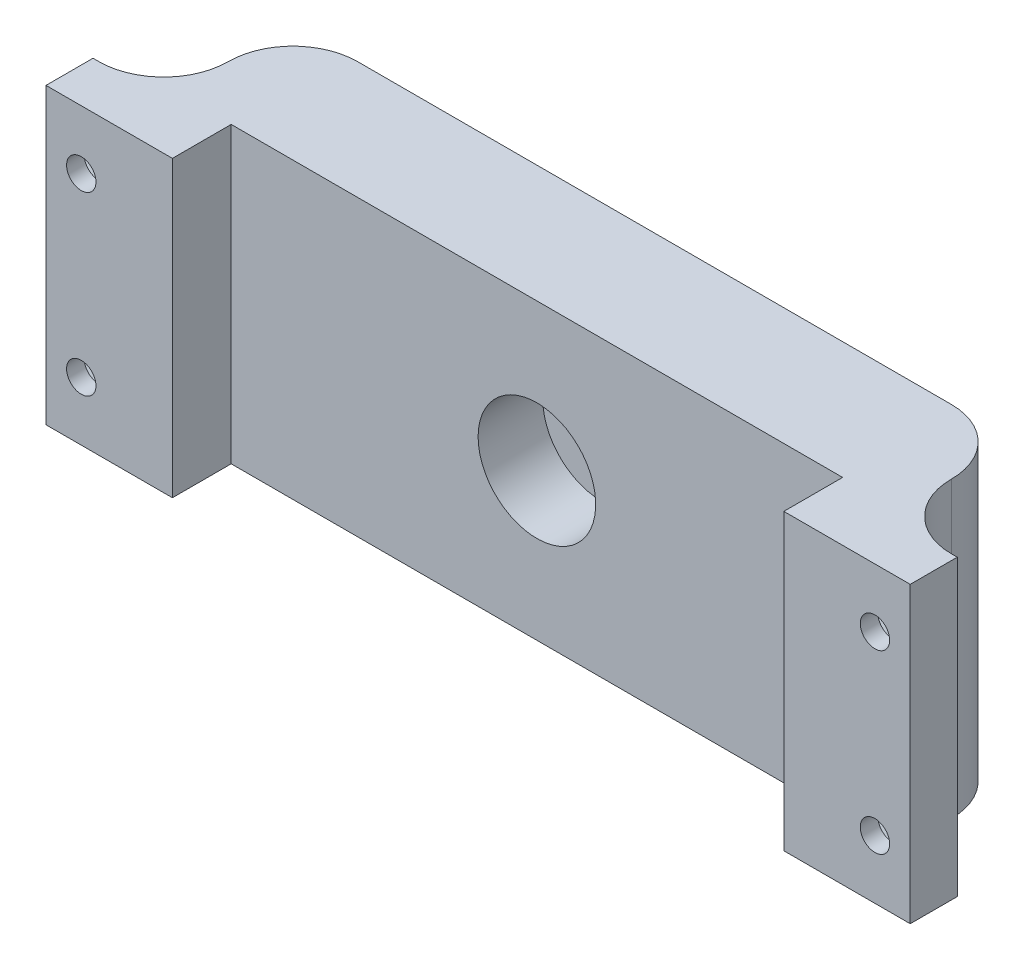
SolidWorks part; units mm, degrees
ref_plane "Alzado" through (0, 0, 0) normal (0, 0, 1) x (1, 0, 0)
ref_plane "Planta" through (0, 0, 0) normal (0, 1, 0) x (1, 0, 0)
ref_plane "Vista lateral" through (0, 0, 0) normal (1, 0, 0) x (0, 0, -1)
sketch "Croquis1" plane through (0, 0, 0) normal (0, 0, 1) x (1, 0, 0)
  line L1 (-61.5, -25) -> (61.5, -25)
  line L2 (-61.5, -25) -> (-61.5, 25)
  line L3 (-61.5, 25) -> (61.5, 25)
  line L4 (61.5, -25) -> (61.5, 25)
  line L5 (-61.5, -25) -> (61.5, 25) construction
  line L6 (-61.5, 25) -> (61.5, -25) construction
  point P0 (0, 0)
  dimension "D1" = 123
  dimension "D2" = 50
extrude "Saliente-Extruir1" add sketch "Croquis1" along normal blind 20
sketch "Croquis2" plane through (0, 0, 20) normal (0, 0, 1) x (1, 0, 0)
  line L0 (-61.5, -25) -> (61.5, -25) construction
  line L1 (-61.5, 25) -> (-50.5, 25)
  line L2 (-61.5, 25) -> (-61.5, -25)
  line L3 (-61.5, -25) -> (-50.5, -25)
  line L4 (-50.5, 25) -> (-50.5, -25)
  line L6 (61.5, 25) -> (50.5, 25)
  line L7 (61.5, 25) -> (61.5, -25)
  line L8 (61.5, -25) -> (50.5, -25)
  line L9 (50.5, 25) -> (50.5, -25)
  dimension "D1" = 11
  dimension "D2" = 11
extrude "Saliente-Extruir2" add sketch "Croquis2" along normal blind 10
sketch "Croquis3" plane through (0, 0, 20) normal (0, 0, 1) x (1, 0, 0)
  line L0 (-50.5, 25) -> (50.5, -25) construction
  circle A0 centre (0, 0) radius 10
  dimension "D1" = 20
extrude "Cortar-Extruir1" cut sketch "Croquis3" against normal blind 11 and the other way through all
sketch "Croquis4" plane through (0, 0, 9) normal (0, 0, 1) x (1, 0, 0)
  circle A0 centre (0, 0) radius 5
  dimension "D1" = 10
extrude "Cortar-Extruir2" cut sketch "Croquis4" against normal blind 7
sketch "Croquis5" plane through (0, 0, 30) normal (0, 0, 1) x (1, 0, 0)
  line L0 (50.5, -25) -> (61.5, -25) construction
  line L1 (61.5, 25) -> (73.5, 25)
  line L2 (61.5, 25) -> (61.5, -25)
  line L3 (61.5, -25) -> (73.5, -25)
  line L4 (73.5, 25) -> (73.5, -25)
  line L5 (-61.5, -25) -> (-50.5, -25) construction
  line L6 (-61.5, 25) -> (-73.5, 25)
  line L7 (-61.5, 25) -> (-61.5, -25)
  line L8 (-61.5, -25) -> (-73.5, -25)
  line L9 (-73.5, 25) -> (-73.5, -25)
  dimension "D1" = 12
  dimension "D2" = 12
extrude "Saliente-Extruir3" add sketch "Croquis5" against normal blind 8
sketch "Croquis7" plane through (0, 0, 22) normal (0, 0, -1) x (-1, 0, 0)
  line L0 (-67.5, 25) -> (-67.5, -25) construction
  line L1 (-73.5, 25) -> (-61.5, 25) construction
  line L2 (-61.5, -25) -> (-73.5, -25) construction
  line L3 (67.5, 25) -> (67.5, -25) construction
  line L4 (61.5, 25) -> (73.5, 25) construction
  line L5 (73.5, -25) -> (61.5, -25) construction
  line L7 (-63.5, 17.3094) -> (-67.5, 19.6188)
  line L8 (-67.5, 19.6188) -> (-71.5, 17.3094)
  line L9 (-71.5, 17.3094) -> (-71.5, 12.6906)
  line L10 (-71.5, 12.6906) -> (-67.5, 10.3812)
  line L11 (-67.5, 10.3812) -> (-63.5, 12.6906)
  line L12 (-63.5, 12.6906) -> (-63.5, 17.3094)
  line L13 (-63.5, -17.3094) -> (-63.5, -12.6906)
  line L14 (-63.5, -12.6906) -> (-67.5, -10.3812)
  line L15 (-67.5, -10.3812) -> (-71.5, -12.6906)
  line L16 (-71.5, -12.6906) -> (-71.5, -17.3094)
  line L17 (-71.5, -17.3094) -> (-67.5, -19.6188)
  line L18 (-67.5, -19.6188) -> (-63.5, -17.3094)
  line L19 (67.5, 10.3812) -> (71.5, 12.6906)
  line L20 (71.5, 12.6906) -> (71.5, 17.3094)
  line L21 (71.5, 17.3094) -> (67.5, 19.6188)
  line L22 (67.5, 19.6188) -> (63.5, 17.3094)
  line L23 (63.5, 17.3094) -> (63.5, 12.6906)
  line L24 (63.5, 12.6906) -> (67.5, 10.3812)
  line L25 (71.5, -12.6906) -> (67.5, -10.3812)
  line L26 (67.5, -10.3812) -> (63.5, -12.6906)
  line L27 (63.5, -12.6906) -> (63.5, -17.3094)
  line L28 (63.5, -17.3094) -> (67.5, -19.6188)
  line L29 (67.5, -19.6188) -> (71.5, -17.3094)
  line L30 (71.5, -17.3094) -> (71.5, -12.6906)
  circle A0 centre (-67.5, 15) radius 4 construction
  circle A1 centre (-67.5, -15) radius 4 construction
  circle A2 centre (67.5, 15) radius 4 construction
  circle A3 centre (67.5, -15) radius 4 construction
  dimension "D1" = 8
  dimension "D2" = 8
  dimension "D3" = 8
  dimension "D4" = 8
  dimension "D5" = 10
  dimension "D6" = 10
  dimension "D7" = 10
  dimension "D8" = 10
extrude "Cortar-Extruir3" cut sketch "Croquis7" against normal blind 5
sketch "Croquis8" plane through (0, 0, 27) normal (0, 0, -1) x (-1, 0, 0)
  line L0 (0, 0) -> (0, 39.6623) construction
  line L1 (-73.5, -25) -> (-73.5, 25) construction
  line L2 (-73.5, 25) -> (-61.5, 25) construction
  line L3 (-61.5, -25) -> (-73.5, -25) construction
  circle A0 centre (-67.5, 15) radius 2.5
  circle A1 centre (-67.5, -15) radius 2.5
  circle A4 centre (67.5, -15) radius 2.5
  circle A5 centre (67.5, 15) radius 2.5
  dimension "D1" = 5
  dimension "D2" = 5
  dimension "D3" = 6
  dimension "D4" = 10
  dimension "D5" = 6
  dimension "D6" = 10
extrude "Cortar-Extruir4" cut sketch "Croquis8" against normal through all both and the other way through all
fillet "Redondeo1" radius 11 4 edges at (61.5, 0, 22) (-61.5, 0, 22) (61.5, 0, 0) (-61.5, 0, 0)
sketch "Croquis9" plane through (0, 0, 30) normal (0, 0, 1) x (1, 0, 0)
  line L0 (73.5, 25) -> (50.5, 25) construction
  line L1 (-52, -25) -> (52, -25)
  line L2 (-52, -25) -> (-52, 25)
  line L3 (-52, 25) -> (52, 25)
  line L4 (52, -25) -> (52, 25)
  line L5 (-52, -25) -> (52, 25) construction
  line L6 (-52, 25) -> (52, -25) construction
  point P0 (0, 0)
  dimension "D1" = 104
extrude "Cortar-Extruir5" cut sketch "Croquis9" against normal up to surface (10 mm away) up to face at (-10, 0, 20)
